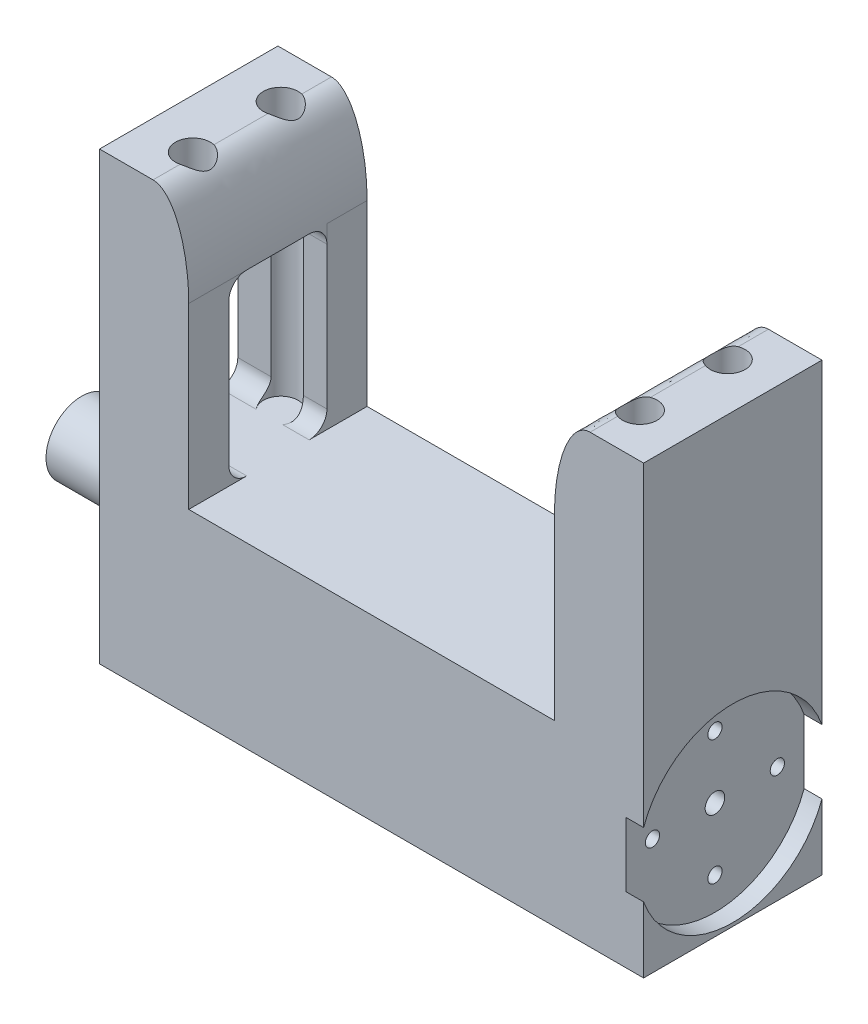
SolidWorks part; units mm, degrees
ref_plane "Ebene vorne" through (0, 0, 0) normal (0, 0, 1) x (1, 0, 0)
ref_plane "Ebene oben" through (0, 0, 0) normal (0, 1, 0) x (1, 0, 0)
ref_plane "Ebene rechts" through (0, 0, 0) normal (1, 0, 0) x (0, 0, -1)
sketch "Skizze1" plane through (0, 0, 0) normal (0, 0, 1) x (1, 0, 0)
  line L1 (0, 0) -> (61, 0)
  line L2 (0, 0) -> (0, 50)
  line L3 (0, 50) -> (61, 50)
  line L4 (61, 0) -> (61, 50)
  dimension "D1" = 61
  dimension "D2" = 50
extrude "Aufsatz-Linear austragen1" add sketch "Skizze1" along normal blind 20
sketch "Skizze2" plane through (0, 50, 0) normal (0, 1, 0) x (1, 0, 0)
  line L0 (61, 0) -> (0, 0) construction
  line L1 (10, 0) -> (51, 0)
  line L2 (10, 0) -> (10, -20)
  line L3 (10, -20) -> (51, -20)
  line L4 (51, 0) -> (51, -20)
  line L5 (61, -20) -> (0, -20) construction
  line L6 (0, -20) -> (0, 0) construction
  dimension "D1" = 41
  dimension "D2" = 10
extrude "Schnitt-Linear austragen1" cut sketch "Skizze2" against normal blind 30
sketch "Skizze3" plane through (61, 0, 0) normal (1, 0, 0) x (0, 0, -1)
  line L0 (-20, 0) -> (0, 0) construction
  line L1 (-15.5, 20) -> (-4.5, 20)
  line L2 (-15.5, 20) -> (-15.5, 40)
  line L3 (-15.5, 40) -> (-4.5, 40)
  line L4 (-4.5, 20) -> (-4.5, 40)
  line L5 (0, 0) -> (0, 50) construction
  dimension "D1" = 20
  dimension "D2" = 11
  dimension "D3" = 20
  dimension "D4" = 4.5
extrude "Schnitt-Linear austragen2" cut sketch "Skizze3" along normal blind 10 from surface starting at face at (0, 25, 10)
sketch "Skizze4" plane through (0, 50, 0) normal (0, 1, 0) x (1, 0, 0)
  line L0 (61, -20) -> (61, 0) construction
  line L1 (0, -20) -> (0, 0) construction
  line L2 (10, 0) -> (0, 0) construction
  line L3 (61, 0) -> (51, 0) construction
  line L4 (61, -20) -> (51, -20) construction
  line L5 (10, -20) -> (0, -20) construction
  circle A0 centre (5.54, -5.225) radius 1.95
  circle A1 centre (5.54, -15.075) radius 1.95
  circle A2 centre (55.66, -15.075) radius 1.95
  circle A4 centre (55.66, -5.225) radius 1.95
  dimension "D1" = 3.9
  dimension "D2" = 3.9
  dimension "D3" = 3.9
  dimension "D4" = 3.9
  dimension "D5" = 5.34
  dimension "D6" = 5.34
  dimension "D7" = 5.54
  dimension "D8" = 5.54
  dimension "D9" = 5.225
  dimension "D10" = 5.225
  dimension "D11" = 4.925
  dimension "D12" = 4.925
extrude "Schnitt-Linear austragen3" cut sketch "Skizze4" against normal up to surface (30 mm away) up to face at (17.75, 20, 10)
fillet "Verrundung1" radius 4 2 edges at (51, 50, 10) (10, 50, 10) second distance 10 first distance on face at (55.66, 50, 7.175) first distance on face at (5.54, 50, 17.025)
fillet "Verrundung2" radius 2 8 edges at (1.8184, 40, 15.5) (1.8649, 40, 4.5) (8.7216, 20, 15.5) (1.8184, 20, 15.5) (8.6751, 20, 4.5) (1.8649, 20, 4.5)
sketch "Skizze6" plane through (61, 0, 0) normal (1, 0, 0) x (0, 0, -1)
  line L1 (-20, 50) -> (0, 50) construction
  circle A0 centre (-10, 11) radius 10.6311
  point P5 (-10, 50)
  dimension "D1" = 21.2622
  dimension "D2" = 39
  dimension "D3" = 0
extrude "Schnitt-Linear austragen4" cut sketch "Skizze6" against normal blind 2
sketch "Skizze7" plane through (59, 0, 0) normal (1, 0, 0) x (0, 0, -1)
  line L0 (-20, 50) -> (0, 50) construction
  line L1 (0, 14.6083) -> (0, 50) construction
  line L2 (0, 0) -> (0, 7.3917) construction
  circle A0 centre (-10, 18) radius 0.8
  circle A1 centre (-3, 11) radius 0.8
  circle A2 centre (-10, 4) radius 0.8
  circle A3 centre (-17, 11) radius 0.8
  dimension "D1" = 32
  dimension "D2" = 14
  dimension "D3" = 7
  dimension "D4" = 7
  dimension "D5" = 7
  dimension "D6" = 7
  dimension "D7" = 10
  dimension "D8" = 1.6
  dimension "D9" = 1.6
  dimension "D10" = 1.6
  dimension "D11" = 1.6
  dimension "D12" = 10
extrude "Schnitt-Linear austragen5" cut sketch "Skizze7" against normal blind 22
sketch "Skizze10" plane through (59, 0, 0) normal (1, 0, 0) x (0, 0, -1)
  circle A0 centre (-10, 11) radius 1.0955
extrude "Schnitt-Linear austragen6" cut sketch "Skizze10" against normal blind 63
sketch "Skizze11" plane through (0, 0, 0) normal (-1, 0, 0) x (0, 0, 1)
  circle A0 centre (10, 11) radius 4
  dimension "D1" = 8
extrude "Aufsatz-Linear austragen3" add sketch "Skizze11" along normal blind 12
